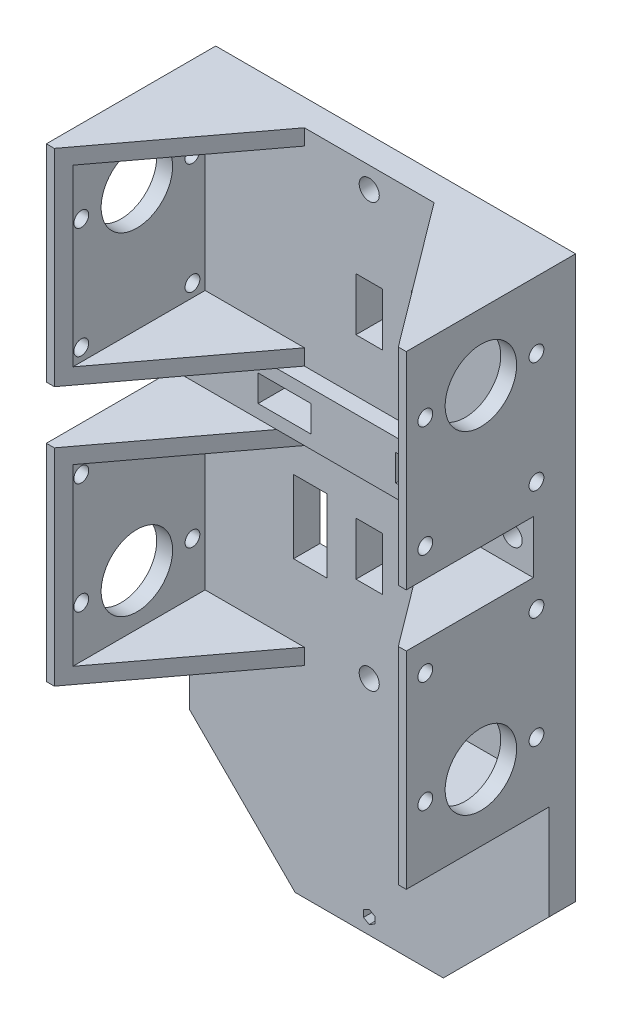
SolidWorks part; units mm, degrees
ref_plane "正面" through (0, 0, 0) normal (0, 0, 1) x (1, 0, 0)
ref_plane "平面" through (0, 0, 0) normal (0, 1, 0) x (1, 0, 0)
ref_plane "右側面" through (0, 0, 0) normal (1, 0, 0) x (0, 0, -1)
sketch "ｽｹｯﾁ5" plane through (0, 0, 0) normal (0, 1, 0) x (1, 0, 0)
  line L0 (-34, -32) -> (-34, 0)
  line L1 (-34, 0) -> (-10, 0)
  line L2 (-10, 0) -> (-34, -32)
  line L3 (-55, 0) -> (55, 0) construction
  dimension "D1" = 24
  dimension "D2" = 32
  dimension "D3" = 10
extrude "ﾎﾞｽ - 押し出し3" add sketch "ｽｹｯﾁ5" against normal blind 39 from offset 5 offset against normal yes
shell "ｼｪﾙ2" thickness 3 removed face at (-22, -24.5, 16)
sketch "ｽｹｯﾁ7" plane through (-31, 0, 0) normal (1, 0, 0) x (0, 0, -1)
  line L0 (-3, -41) -> (-3, -8) construction
  line L1 (-26.4, -31.4) -> (-5.4, -31.4) construction
  line L2 (-26.4, -31.4) -> (-26.4, -10.4) construction
  line L3 (-26.4, -10.4) -> (-5.4, -10.4) construction
  line L4 (-5.4, -31.4) -> (-5.4, -10.4) construction
  line L5 (-3, -8) -> (-28, -8) construction
  circle A0 centre (-15.9, -31.4) radius 6.75
  circle A1 centre (-26.4, -31.4) radius 1.4
  circle A2 centre (-5.4, -31.4) radius 1.4
  circle A3 centre (-5.4, -10.4) radius 1.4
  circle A4 centre (-26.4, -10.4) radius 1.4
  point P10 (-15.9, -31.4)
  dimension "D3" = 2.8
  dimension "D6" = 13.5
  dimension "D1" = 21
  dimension "D2" = 21
  dimension "D4" = 2.4
  dimension "D5" = 2.4
extrude "ｶｯﾄ - 押し出し5" cut sketch "ｽｹｯﾁ7" against normal through all
sketch "ｽｹｯﾁ1" plane through (0, 0, 0) normal (0, 0, 1) x (1, 0, 0)
  line L0 (-34, -44) -> (-34, -5) construction
  line L1 (34, -44) -> (-34, -44)
  line L2 (34, -44) -> (34, 44)
  line L3 (34, 44) -> (-34, 44)
  line L4 (-34, -44) -> (-34, 44)
  line L5 (34, -44) -> (-34, 44) construction
  line L6 (34, 44) -> (-34, -44) construction
  line L7 (-34, -44) -> (-10, -44) construction
  point P0 (0, 0)
extrude "ﾎﾞｽ - 押し出し1" add sketch "ｽｹｯﾁ1" along normal blind 3 and the other way blind 2 contours L4 L1 L2 L3
sketch "ｽｹｯﾁ8" plane through (0, 0, 0) normal (0, 0, 1) x (1, 0, 0)
  line L0 (-34, -44) -> (-34, -5) construction
  line L1 (-34, -5) -> (-22.8121, -5)
  line L2 (-34, -5) -> (-34, -44)
  line L3 (-34, -44) -> (-22.8121, -44)
  line L4 (-22.8121, -5) -> (-22.8121, -44)
extrude "ｶｯﾄ - 押し出し6" cut sketch "ｽｹｯﾁ8" against normal blind 2 from vertex starting at point (-34, -5, 32)
mirror "ﾐﾗｰ1" about plane through (0, 0, 0) normal (1, 0, 0) of bodies 136 101
mirror "ﾐﾗｰ2" about plane through (0, 0, 0) normal (0, 1, 0) of bodies 134
sketch "ｽｹｯﾁ9" plane through (0, 0, 3) normal (0, 0, 1) x (1, 0, 0)
  circle A0 centre (-30, 0) radius 1.9
  circle A1 centre (0, 40) radius 1.9
  circle A2 centre (30, 0) radius 1.9
  circle A3 centre (0, -40) radius 1.9
  dimension "D1" = 3.8
  dimension "D2" = 30
  dimension "D3" = 30
  dimension "D4" = 40
  dimension "D5" = 40
extrude "ｶｯﾄ - 押し出し7" cut sketch "ｽｹｯﾁ9" against normal blind 10
sketch "ｽｹｯﾁ10" plane through (0, 0, 3) normal (0, 0, 1) x (1, 0, 0)
  line L1 (2.5, -25) -> (-2.5, -25)
  line L2 (2.5, -25) -> (2.5, -15)
  line L3 (2.5, -15) -> (-2.5, -15)
  line L4 (-2.5, -25) -> (-2.5, -15)
  line L5 (2.5, -25) -> (-2.5, -15) construction
  line L6 (2.5, -15) -> (-2.5, -25) construction
  line L7 (2.5, 15) -> (-2.5, 15)
  line L8 (2.5, 15) -> (2.5, 25)
  line L9 (2.5, 25) -> (-2.5, 25)
  line L10 (-2.5, 15) -> (-2.5, 25)
  line L11 (2.5, 15) -> (-2.5, 25) construction
  line L12 (2.5, 25) -> (-2.5, 15) construction
  point P0 (0, -20)
  point P5 (0, 20)
  dimension "D1" = 5
  dimension "D2" = 10
  dimension "D3" = 20
  dimension "D4" = 20
extrude "ｶｯﾄ - 押し出し8" cut sketch "ｽｹｯﾁ10" against normal blind 10
sketch "ｽｹｯﾁ11" plane through (0, 0, 3) normal (0, 0, 1) x (1, 0, 0)
  line L0 (31, 38.15) -> (31, 24.65) construction
  line L1 (14.3, 13.75) -> (8, 13.75)
  line L2 (14.3, 13.75) -> (14.3, 27.55)
  line L3 (14.3, 27.55) -> (8, 27.55)
  line L4 (8, 13.75) -> (8, 27.55)
  line L5 (14.3, 13.75) -> (8, 27.55) construction
  line L6 (14.3, 27.55) -> (8, 13.75) construction
  line L7 (-8, -27.55) -> (-14.3, -27.55)
  line L8 (-8, -27.55) -> (-8, -13.75)
  line L9 (-8, -13.75) -> (-14.3, -13.75)
  line L10 (-14.3, -27.55) -> (-14.3, -13.75)
  line L11 (-8, -27.55) -> (-14.3, -13.75) construction
  line L12 (-8, -13.75) -> (-14.3, -27.55) construction
  line L13 (31, 38.15) -> (31, 24.65)
  line L15 (-31, -38.15) -> (-31, -24.65) construction
  line L16 (-31, -38.15) -> (-31, -24.65)
  point P0 (11.15, 20.65)
  point P5 (-11.15, -20.65)
  point P15 (31, 31.4)
  point P20 (-31, -31.4)
  dimension "D1" = 6.3
  dimension "D2" = 3.85
  dimension "D3" = 17.65
  dimension "D4" = 23
  dimension "D5" = 3.85
  dimension "D6" = 23
extrude "ｶｯﾄ - 押し出し9" cut sketch "ｽｹｯﾁ11" against normal blind 10 contours L10 L7 L8 L9 | L4 L1 L2 L3 region at (11.15, 20.65, 3) region at (-11.15, -20.65, 3)
sketch "ｽｹｯﾁ12" plane through (0, 0, 3) normal (0, 0, 1) x (1, 0, 0)
  line L1 (-8, -2.5) -> (-18, -2.5)
  line L2 (-8, -2.5) -> (-8, 2.5)
  line L3 (-8, 2.5) -> (-18, 2.5)
  line L4 (-18, -2.5) -> (-18, 2.5)
  line L5 (-8, -2.5) -> (-18, 2.5) construction
  line L6 (-8, 2.5) -> (-18, -2.5) construction
  line L7 (18, -2.5) -> (8, -2.5)
  line L8 (18, -2.5) -> (18, 2.5)
  line L9 (18, 2.5) -> (8, 2.5)
  line L10 (8, -2.5) -> (8, 2.5)
  line L11 (18, -2.5) -> (8, 2.5) construction
  line L12 (18, 2.5) -> (8, -2.5) construction
  point P0 (-13, 0)
  point P5 (13, 0)
  dimension "D1" = 5
  dimension "D2" = 10
  dimension "D3" = 13
  dimension "D4" = 13
extrude "ｶｯﾄ - 押し出し10" cut sketch "ｽｹｯﾁ12" against normal blind 10
sketch "ｽｹｯﾁ13" plane through (0, -44, 0) normal (0, -1, 0) x (1, 0, 0)
  line L0 (34, -2) -> (34, 30) construction
  line L1 (-34, -2) -> (34, -2)
  line L2 (-34, -2) -> (-34, 3)
  line L3 (-34, 3) -> (34, 3)
  line L4 (34, -2) -> (34, 3)
  line L5 (12.25, 3) -> (-12.25, 3) construction
extrude "ﾎﾞｽ - 押し出し4" add sketch "ｽｹｯﾁ13" along normal blind 38
chamfer "面取り2" distance 20 angle 45 2 edges at (-34, -82, 0.5) (34, -82, 0.5)
sketch "ｽｹｯﾁ14" plane through (0, 0, -2) normal (0, 0, -1) x (-1, 0, 0)
  line L0 (14, -82) -> (-14, -82) construction
  line L1 (23.4, -79) -> (-23.4, -79) construction
  line L2 (23.4, -79) -> (23.4, -47.08) construction
  line L3 (23.4, -47.08) -> (-23.4, -47.08) construction
  line L4 (-23.4, -79) -> (-23.4, -47.08) construction
  line L5 (23.4, -79) -> (-23.4, -47.08) construction
  line L6 (23.4, -47.08) -> (-23.4, -79) construction
  line L8 (-23.4, -45.83) -> (-24.4825, -46.455)
  line L9 (-24.4825, -46.455) -> (-24.4825, -47.705)
  line L10 (-24.4825, -47.705) -> (-23.4, -48.33)
  line L11 (-23.4, -48.33) -> (-22.3175, -47.705)
  line L12 (-22.3175, -47.705) -> (-22.3175, -46.455)
  line L13 (-22.3175, -46.455) -> (-23.4, -45.83)
  line L14 (23.4, -45.83) -> (22.3175, -46.455)
  line L15 (22.3175, -46.455) -> (22.3175, -47.705)
  line L16 (22.3175, -47.705) -> (23.4, -48.33)
  line L17 (23.4, -48.33) -> (24.4825, -47.705)
  line L18 (24.4825, -47.705) -> (24.4825, -46.455)
  line L19 (24.4825, -46.455) -> (23.4, -45.83)
  line L20 (0, -77.75) -> (-1.0825, -78.375)
  line L21 (-1.0825, -78.375) -> (-1.0825, -79.625)
  line L22 (-1.0825, -79.625) -> (0, -80.25)
  line L23 (0, -80.25) -> (1.0825, -79.625)
  line L24 (1.0825, -79.625) -> (1.0825, -78.375)
  line L25 (1.0825, -78.375) -> (0, -77.75)
  circle A0 centre (-23.4, -47.08) radius 1.5
  circle A1 centre (23.4, -47.08) radius 1.5
  circle A2 centre (0, -79) radius 1.5
  circle A3 centre (-23.4, -47.08) radius 1.0825 construction
  circle A4 centre (23.4, -47.08) radius 1.0825 construction
  circle A5 centre (0, -79) radius 1.0825 construction
  point P0 (0, -63.04)
  point P12 (0, -82)
  dimension "D3" = 3
  dimension "D1" = 46.8
  dimension "D2" = 31.92
  dimension "D4" = 3
  dimension "D5" = 2.5
extrude "ｶｯﾄ - 押し出し11" cut sketch "ｽｹｯﾁ14" against normal blind 35 contours L24 L25 L20 L21 L22 L23 | L12 L13 L8 L9 L10 L11 | L18 L19 L14 L15 L16 L17 region at (23.4, -47.08, -2) region at (-23.4, -47.08, -2) region at (0, -79, -2)
sketch "ｽｹｯﾁ15" plane through (0, 0, 3) normal (0, 0, 1) x (1, 0, 0)
  line L0 (-18, 2.5) -> (-18, -2.5) construction
  line L1 (34, -5) -> (-34, -5)
  line L2 (34, -5) -> (34, 5)
  line L3 (34, 5) -> (-34, 5)
  line L4 (-34, -5) -> (-34, 5)
  line L5 (-18, -2.5) -> (-8, -2.5) construction
  line L6 (-8, 2.5) -> (-18, 2.5) construction
  line L7 (-8, -2.5) -> (-8, 2.5) construction
  line L8 (8, 2.5) -> (8, -2.5) construction
  line L9 (18, 2.5) -> (8, 2.5) construction
  line L10 (8, -2.5) -> (18, -2.5) construction
  line L11 (18, -2.5) -> (18, 2.5) construction
  line L12 (-18, 2.5) -> (-18, -2.5)
  line L13 (-18, -2.5) -> (-8, -2.5)
  line L14 (-8, 2.5) -> (-18, 2.5)
  line L15 (-8, -2.5) -> (-8, 2.5)
  line L16 (8, 2.5) -> (8, -2.5)
  line L17 (18, 2.5) -> (8, 2.5)
  line L18 (8, -2.5) -> (18, -2.5)
  line L19 (18, -2.5) -> (18, 2.5)
  circle A0 centre (30, 0) radius 1.9 construction
  circle A1 centre (-30, 0) radius 1.9 construction
  circle A2 centre (30, 0) radius 1.9
  circle A3 centre (-30, 0) radius 1.9
extrude "ﾎﾞｽ - 押し出し5" add sketch "ｽｹｯﾁ15" along normal blind 3
equation "\"D3@ｽｹｯﾁ9\"=\"D2@ｽｹｯﾁ9\""
equation "\"D5@ｽｹｯﾁ9\"=\"D4@ｽｹｯﾁ9\""
equation "\"D4@ｽｹｯﾁ10\"=\"D3@ｽｹｯﾁ10\""
equation "\"D4@ｽｹｯﾁ11\"=26-3"
equation "\"D6@ｽｹｯﾁ11\"=26-3"
equation "\"D4@ｽｹｯﾁ12\"=\"D3@ｽｹｯﾁ12\""
